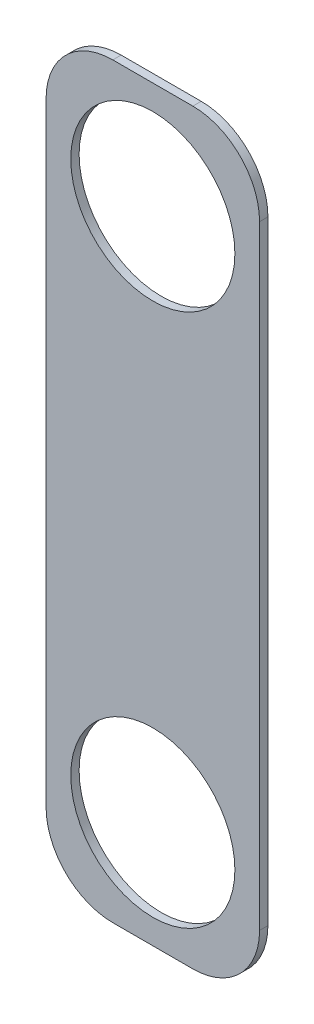
SolidWorks part; units mm, degrees
material "6061 Alloy"
ref_plane "Front Plane" through (0, 0, 0) normal (0, 0, 1) x (1, 0, 0)
ref_plane "Top Plane" through (0, 0, 0) normal (0, 1, 0) x (1, 0, 0)
ref_plane "Right Plane" through (0, 0, 0) normal (1, 0, 0) x (0, 0, -1)
sketch "Sketch1" plane through (0, 0, 0) normal (0, 0, 1) x (1, 0, 0)
  line L0 (0, 0) -> (0, -101.6) construction
  line L2 (-7.62, 20.32) -> (7.62, 20.32)
  line L3 (-20.32, 7.62) -> (-20.32, -109.22)
  line L4 (-7.62, -121.92) -> (7.62, -121.92)
  line L5 (20.32, 7.62) -> (20.32, -109.22)
  circle A0 centre (0, 0) radius 38.1 construction
  circle A1 centre (0, -101.6) radius 38.1 construction
  circle A2 centre (0, 0) radius 15.621
  circle A3 centre (0, -101.6) radius 15.621
  arc A4 (7.62, -121.92) -> (20.32, -109.22) centre (7.62, -109.22) ccw
  arc A5 (-20.32, -109.22) -> (-7.62, -121.92) centre (-7.62, -109.22) ccw
  arc A6 (7.62, 20.32) -> (20.32, 7.62) centre (7.62, 7.62) cw
  arc A7 (-7.62, 20.32) -> (-20.32, 7.62) centre (-7.62, 7.62) ccw
  point P3 (0, 0)
  point P5 (0, 0)
  point P20 (20.32, 20.32)
  point P23 (-20.32, 20.32)
  dimension "D2" = 76.2
  dimension "D3" = 76.2
  dimension "D4" = 31.242
  dimension "D5" = 31.242
  dimension "D10" = 12.7
  dimension "D1" = 101.6
  dimension "D6" = 40.64
  dimension "D7" = 20.32
  dimension "D8" = 20.32
  dimension "D9" = 20.32
extrude "Boss-Extrude1" add sketch "Sketch1" along normal blind 1.5875
